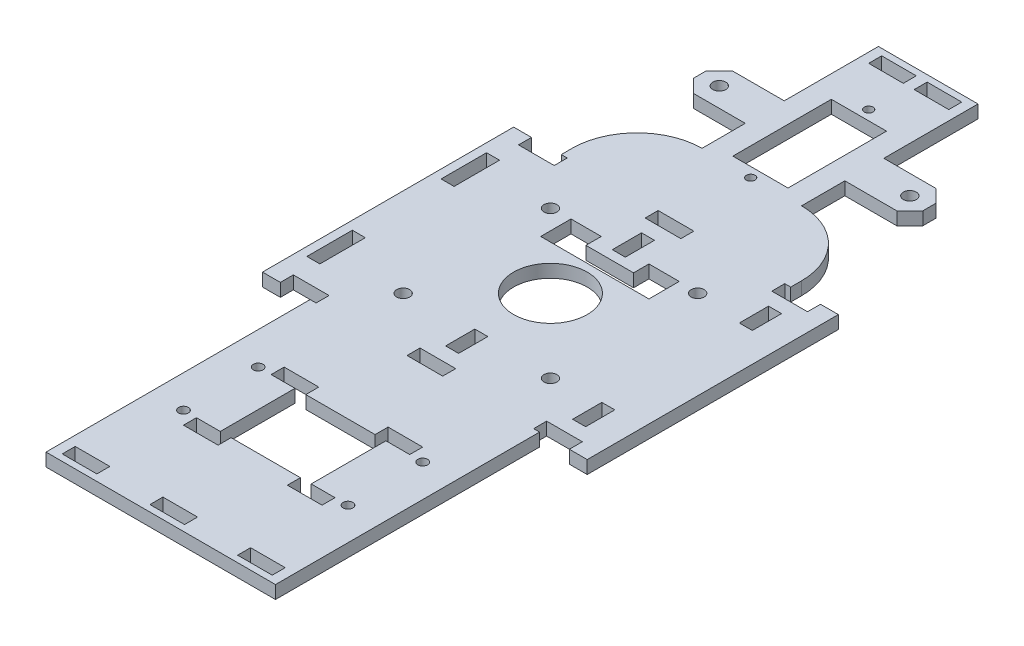
SolidWorks part; units mm, degrees
ref_plane "Front Plane" through (0, 0, 0) normal (0, 0, 1) x (1, 0, 0)
ref_plane "Top Plane" through (0, 0, 0) normal (0, 1, 0) x (1, 0, 0)
ref_plane "Right Plane" through (0, 0, 0) normal (1, 0, 0) x (0, 0, -1)
sketch "Sketch1" plane through (0, 0, 0) normal (0, 1, 0) x (1, 0, 0)
  line L1 (-12.9418, -76.5) -> (40.0582, -76.5)
  line L2 (-12.9418, -76.5) -> (-12.9418, 76.5)
  line L3 (-12.9418, 76.5) -> (40.0582, 76.5)
  line L4 (40.0582, -76.5) -> (40.0582, 76.5)
  point P0 (0, 0)
  dimension "D1" = 153
  dimension "D2" = 53
extrude "Boss-Extrude1" add sketch "Sketch1" along normal blind 3
sketch "Sketch2" plane through (0, 3, 0) normal (0, 1, 0) x (1, 0, 0)
  line L0 (-12.9418, 76.5) -> (-12.9418, -76.5) construction
  line L1 (-12.9418, -76.5) -> (40.0582, -76.5) construction
  line L2 (40.0582, -76.5) -> (40.0582, 76.5) construction
  circle A0 centre (-5.4418, -68.25) radius 1.125
  circle A1 centre (-5.4418, -51) radius 1.125
  circle A2 centre (32.5582, -68.25) radius 1.125
  circle A3 centre (32.5582, -51) radius 1.125
  dimension "D1" = 2.25
  dimension "D4" = 2.25
  dimension "D6" = 2.25
  dimension "D7" = 2.25
  dimension "D2" = 7.5
  dimension "D3" = 8.25
  dimension "D5" = 17.25
  dimension "D8" = 7.5
  dimension "D9" = 7.5
  dimension "D10" = 17.25
  dimension "D11" = 7.5
  dimension "D12" = 8.25
extrude "Cut-Extrude1" cut sketch "Sketch2" against normal blind 3
sketch "Sketch4" plane through (40.0582, 0, 0) normal (1, 0, 0) x (0, 0, -1)
  line L0 (-76.5, 3) -> (76.5, 3) construction
  line L1 (-31.5, 3) -> (26.5, 3)
  line L2 (-31.5, 3) -> (-31.5, 0)
  line L3 (-31.5, 0) -> (26.5, 0)
  line L4 (26.5, 3) -> (26.5, 0)
  line L5 (-76.5, 0) -> (76.5, 0) construction
  line L6 (76.5, 3) -> (76.5, 0) construction
  dimension "D1" = 50
  dimension "D2" = 58
extrude "Boss-Extrude3" add sketch "Sketch4" along normal blind 4.5
sketch "Sketch5" plane through (-12.9418, 0, 0) normal (-1, 0, 0) x (0, 0, 1)
  line L0 (-76.5, 0) -> (76.5, 0) construction
  line L1 (31.5, 0) -> (-26.5, 0)
  line L2 (31.5, 0) -> (31.5, 3)
  line L3 (31.5, 3) -> (-26.5, 3)
  line L4 (-26.5, 0) -> (-26.5, 3)
  line L5 (-76.5, 3) -> (76.5, 3) construction
  line L6 (-76.5, 3) -> (-76.5, 0) construction
  dimension "D1" = 50
  dimension "D2" = 58
extrude "Boss-Extrude4" add sketch "Sketch5" along normal blind 4.5
sketch "Sketch8" plane through (0, 3, 0) normal (0, 1, 0) x (1, 0, 0)
  line L1 (-12.9418, 76.5) -> (2.0582, 76.5)
  line L2 (-12.9418, 76.5) -> (-12.9418, 63)
  line L3 (-12.9418, 63) -> (2.0582, 63)
  line L4 (2.0582, 76.5) -> (2.0582, 63)
  line L5 (40.0582, 76.5) -> (25.0582, 76.5)
  line L6 (40.0582, 76.5) -> (40.0582, 63)
  line L7 (40.0582, 63) -> (25.0582, 63)
  line L8 (25.0582, 76.5) -> (25.0582, 63)
  dimension "D1" = 13.5
  dimension "D2" = 15
extrude "Cut-Extrude3" cut sketch "Sketch8" against normal blind 3
sketch "Sketch9" plane through (0, 3, 0) normal (0, 1, 0) x (1, 0, 0)
  line L1 (-12.9418, 63) -> (-6.9418, 63)
  line L2 (-12.9418, 63) -> (-12.9418, 54)
  line L3 (-12.9418, 54) -> (-6.9418, 54)
  line L4 (-6.9418, 63) -> (-6.9418, 54)
  line L5 (40.0582, 63) -> (34.0582, 63)
  line L6 (40.0582, 63) -> (40.0582, 54)
  line L7 (40.0582, 54) -> (34.0582, 54)
  line L8 (34.0582, 63) -> (34.0582, 54)
  dimension "D1" = 9
  dimension "D2" = 6
extrude "Cut-Extrude4" cut sketch "Sketch9" against normal blind 3
sketch "Sketch10" plane through (0, 3, 0) normal (0, 1, 0) x (1, 0, 0)
  line L0 (-17.4418, 26.5) -> (-12.9418, 26.5) construction
  line L1 (-12.9418, 54) -> (2.0582, 54)
  line L2 (-12.9418, 54) -> (-12.9418, 44)
  line L3 (-12.9418, 44) -> (2.0582, 44)
  line L4 (2.0582, 54) -> (2.0582, 44)
  line L5 (40.0582, 54) -> (25.0582, 54)
  line L6 (40.0582, 54) -> (40.0582, 44)
  line L7 (40.0582, 44) -> (25.0582, 44)
  line L8 (25.0582, 54) -> (25.0582, 44)
  dimension "D1" = 17.5
extrude "Cut-Extrude5" cut sketch "Sketch10" against normal blind 3
sketch "Sketch11" plane through (0, 3, 0) normal (0, 1, 0) x (1, 0, 0)
  line L0 (-17.4418, 26.5) -> (-12.9418, 26.5) construction
  line L1 (7.1832, 68.75) -> (19.9332, 68.75)
  line L2 (7.1832, 68.75) -> (7.1832, 46)
  line L3 (7.1832, 46) -> (19.9332, 46)
  line L4 (19.9332, 68.75) -> (19.9332, 46)
  line L6 (25.0582, 54) -> (25.0582, 44) construction
  dimension "D1" = 12.75
  dimension "D2" = 22.75
  dimension "D3" = 19.5
  dimension "D4" = 5.125
extrude "Cut-Extrude6" cut sketch "Sketch11" against normal blind 3
sketch "Sketch12" plane through (0, 3, 0) normal (0, 1, 0) x (1, 0, 0)
  line L0 (7.1832, 46) -> (19.9332, 46) construction
  line L1 (19.9332, 68.75) -> (7.1832, 68.75) construction
  line L2 (19.9332, 46) -> (19.9332, 68.75) construction
  circle A0 centre (13.5582, 71) radius 1
  circle A1 centre (13.5582, 43.75) radius 1
  dimension "D3" = 2
  dimension "D4" = 2
  dimension "D1" = 2.25
  dimension "D2" = 2.25
  dimension "D5" = 6.375
  dimension "D6" = 6.375
extrude "Cut-Extrude7" cut sketch "Sketch12" against normal blind 3
sketch "Sketch17" plane through (-6.9418, 0, 0) normal (-1, 0, 0) x (0, 0, 1)
  line L1 (-63, 3) -> (-54, 3)
  line L2 (-63, 3) -> (-63, 0)
  line L3 (-63, 0) -> (-54, 0)
  line L4 (-54, 3) -> (-54, 0)
extrude "Boss-Extrude6" add sketch "Sketch17" along normal blind 6
sketch "Sketch18" plane through (34.0582, 0, 0) normal (1, 0, 0) x (0, 0, -1)
  line L1 (54, 3) -> (63, 3)
  line L2 (54, 3) -> (54, 0)
  line L3 (54, 0) -> (63, 0)
  line L4 (63, 3) -> (63, 0)
extrude "Boss-Extrude8" add sketch "Sketch18" along normal blind 6
sketch "Sketch19" plane through (0, 3, 0) normal (0, 1, 0) x (1, 0, 0)
  line L0 (40.0582, 63) -> (40.0582, 54) construction
  line L1 (25.0582, 63) -> (40.0582, 63) construction
  line L2 (-12.9418, 63) -> (2.0582, 63) construction
  line L3 (-12.9418, 54) -> (-12.9418, 63) construction
  circle A0 centre (35.5582, 58.5) radius 1.5
  circle A1 centre (-8.4418, 58.5) radius 1.5
  dimension "D3" = 3
  dimension "D4" = 3
  dimension "D1" = 4.5
  dimension "D2" = 4.5
  dimension "D5" = 4.5
  dimension "D6" = 4.5
extrude "Cut-Extrude11" cut sketch "Sketch19" against normal blind 3
sketch "Sketch20" plane through (44.5582, 0, 0) normal (1, 0, 0) x (0, 0, -1)
  line L1 (-31.5, 3) -> (26.5, 3)
  line L2 (-31.5, 3) -> (-31.5, 0)
  line L3 (-31.5, 0) -> (26.5, 0)
  line L4 (26.5, 3) -> (26.5, 0)
extrude "Boss-Extrude9" add sketch "Sketch20" along normal blind 6.5
sketch "Sketch21" plane through (-17.4418, 0, 0) normal (-1, 0, 0) x (0, 0, 1)
  line L1 (-26.5, 3) -> (31.5, 3)
  line L2 (-26.5, 3) -> (-26.5, 0)
  line L3 (-26.5, 0) -> (31.5, 0)
  line L4 (31.5, 3) -> (31.5, 0)
extrude "Boss-Extrude10" add sketch "Sketch21" along normal blind 6.5
sketch "Sketch29" plane through (0, 3, 0) normal (0, 1, 0) x (1, 0, 0)
  line L1 (-2.4418, -48) -> (5.5582, -48)
  line L2 (-2.4418, -48) -> (-2.4418, -51)
  line L3 (-2.4418, -51) -> (5.5582, -51)
  line L4 (5.5582, -48) -> (5.5582, -51)
  line L5 (-2.4418, -68.25) -> (5.5582, -68.25)
  line L6 (-2.4418, -68.25) -> (-2.4418, -71.25)
  line L7 (-2.4418, -71.25) -> (5.5582, -71.25)
  line L8 (5.5582, -68.25) -> (5.5582, -71.25)
  line L9 (21.5582, -48) -> (29.5582, -48)
  line L10 (21.5582, -48) -> (21.5582, -51)
  line L11 (21.5582, -51) -> (29.5582, -51)
  line L12 (29.5582, -48) -> (29.5582, -51)
  line L13 (21.5582, -68.25) -> (29.5582, -68.25)
  line L14 (21.5582, -68.25) -> (21.5582, -71.25)
  line L15 (21.5582, -71.25) -> (29.5582, -71.25)
  line L16 (29.5582, -68.25) -> (29.5582, -71.25)
  circle A1 centre (-5.4418, -51) radius 1.125 construction
  circle A2 centre (32.5582, -51) radius 1.125 construction
  circle A3 centre (-5.4418, -68.25) radius 1.125 construction
  circle A4 centre (32.5582, -68.25) radius 1.125 construction
  dimension "D1" = 8
  dimension "D2" = 3
  dimension "D3" = 3
  dimension "D4" = 8
  dimension "D5" = 8
  dimension "D6" = 3
  dimension "D7" = 8
  dimension "D8" = 3
  dimension "D9" = 0
  dimension "D10" = 0
  dimension "D11" = 0
  dimension "D12" = 0
  dimension "D13" = 3
  dimension "D14" = 3
  dimension "D15" = 3
  dimension "D16" = 3
extrude "Cut-Extrude15" cut sketch "Sketch29" against normal blind 3
sketch "Sketch33" plane through (0, 3, 0) normal (0, 1, 0) x (1, 0, 0)
  line L0 (-2.4418, -51) -> (5.5582, -51) construction
  line L1 (3.0582, -51) -> (24.0582, -51)
  line L2 (3.0582, -51) -> (3.0582, -68.25)
  line L3 (3.0582, -68.25) -> (24.0582, -68.25)
  line L4 (24.0582, -51) -> (24.0582, -68.25)
  line L5 (29.5582, -68.25) -> (21.5582, -68.25) construction
  line L6 (-12.9418, -31.5) -> (-12.9418, -76.5) construction
  line L7 (40.0582, -76.5) -> (40.0582, -31.5) construction
  dimension "D1" = 16
  dimension "D2" = 16
extrude "Cut-Extrude20" cut sketch "Sketch33" against normal blind 3
chamfer "Chamfer1" distance 3 angle 45 1 edges at (-12.9418, 1.5, -54)
chamfer "Chamfer2" distance 3 angle 45 1 edges at (-12.9418, 1.5, -63)
chamfer "Chamfer3" distance 3 angle 45 1 edges at (40.0582, 1.5, -54)
chamfer "Chamfer4" distance 3 angle 45 1 edges at (40.0582, 1.5, -63)
sketch "Sketch34" plane through (0, 3, 0) normal (0, 1, 0) x (1, 0, 0)
  line L0 (-23.9418, 26.5) -> (-12.9418, 26.5) construction
  line L1 (-19.8168, 26.5) -> (-11.5668, 26.5)
  line L2 (-19.8168, 26.5) -> (-19.8168, 23.5)
  line L3 (-19.8168, 23.5) -> (-11.5668, 23.5)
  line L4 (-11.5668, 26.5) -> (-11.5668, 23.5)
  line L5 (51.0582, 26.5) -> (40.0582, 26.5) construction
  line L6 (46.9332, 26.5) -> (38.6832, 26.5)
  line L7 (46.9332, 26.5) -> (46.9332, 23.5)
  line L8 (46.9332, 23.5) -> (38.6832, 23.5)
  line L9 (38.6832, 26.5) -> (38.6832, 23.5)
  line L11 (-23.9418, -31.5) -> (-12.9418, -31.5) construction
  line L12 (-19.8168, -31.5) -> (-11.5668, -31.5)
  line L13 (-19.8168, -31.5) -> (-19.8168, -28.5)
  line L14 (-19.8168, -28.5) -> (-11.5668, -28.5)
  line L15 (-11.5668, -31.5) -> (-11.5668, -28.5)
  line L16 (51.0582, -31.5) -> (40.0582, -31.5) construction
  line L17 (46.9332, -31.5) -> (38.6832, -31.5)
  line L18 (46.9332, -31.5) -> (46.9332, -28.5)
  line L19 (46.9332, -28.5) -> (38.6832, -28.5)
  line L20 (38.6832, -31.5) -> (38.6832, -28.5)
  line L21 (-23.9418, -31.5) -> (-23.9418, 26.5) construction
  line L22 (9.4332, -28.5) -> (17.6832, -28.5)
  line L23 (9.4332, -28.5) -> (9.4332, -31.5)
  line L24 (9.4332, -31.5) -> (17.6832, -31.5)
  line L25 (17.6832, -28.5) -> (17.6832, -31.5)
  line L26 (9.4332, 26.5) -> (17.6832, 26.5)
  line L27 (9.4332, 26.5) -> (9.4332, 23.5)
  line L28 (9.4332, 23.5) -> (17.6832, 23.5)
  line L29 (17.6832, 26.5) -> (17.6832, 23.5)
  line L30 (51.0582, 26.5) -> (51.0582, -31.5) construction
  dimension "D1" = 4.125
  dimension "D2" = 4.125
  dimension "D3" = 8.25
  dimension "D4" = 8.25
  dimension "D5" = 8.25
  dimension "D6" = 33.375
  dimension "D7" = 8.25
  dimension "D8" = 8.25
  dimension "D9" = 8.25
  dimension "D10" = 4.125
  dimension "D11" = 4.125
  dimension "D12" = 33.375
  dimension "D13" = 3
  dimension "D14" = 3
  dimension "D15" = 3
  dimension "D16" = 3
  dimension "D17" = 3
  dimension "D18" = 3
extrude "Cut-Extrude21" cut sketch "Sketch34" against normal blind 3
sketch "Sketch35" plane through (0, 3, 0) normal (0, 1, 0) x (1, 0, 0)
  line L0 (51.0582, 26.5) -> (51.0582, -31.5) construction
  line L1 (41.3082, 20.125) -> (44.3082, 20.125)
  line L2 (41.3082, 20.125) -> (41.3082, 13.375)
  line L3 (41.3082, 13.375) -> (44.3082, 13.375)
  line L4 (44.3082, 20.125) -> (44.3082, 13.375)
  line L9 (38.6832, 23.5) -> (46.9332, 23.5) construction
  line L10 (46.9332, -28.5) -> (38.6832, -28.5) construction
  line L11 (41.3082, -18.375) -> (44.3082, -18.375)
  line L12 (41.3082, -18.375) -> (41.3082, -25.125)
  line L13 (41.3082, -25.125) -> (44.3082, -25.125)
  line L14 (44.3082, -18.375) -> (44.3082, -25.125)
  dimension "D1" = 6.75
  dimension "D2" = 6.75
  dimension "D3" = 3
  dimension "D4" = 3.375
  dimension "D5" = 3.375
  dimension "D6" = 6.75
extrude "Cut-Extrude22" cut sketch "Sketch35" against normal blind 3
sketch "Sketch36" plane through (0, 3, 0) normal (0, 1, 0) x (1, 0, 0)
  line L0 (17.6832, -28.5) -> (9.4332, -28.5) construction
  line L1 (11.9747, 20.125) -> (14.9747, 20.125)
  line L2 (11.9747, 20.125) -> (11.9747, 13.375)
  line L3 (11.9747, 13.375) -> (14.9747, 13.375)
  line L4 (14.9747, 20.125) -> (14.9747, 13.375)
  line L5 (11.9747, -18.375) -> (14.9747, -18.375)
  line L6 (11.9747, -18.375) -> (11.9747, -25.125)
  line L7 (11.9747, -25.125) -> (14.9747, -25.125)
  line L8 (14.9747, -18.375) -> (14.9747, -25.125)
  line L9 (9.4332, 23.5) -> (17.6832, 23.5) construction
  dimension "D1" = 3
  dimension "D2" = 6.75
  dimension "D3" = 3
  dimension "D4" = 6.75
  dimension "D5" = 3.375
  dimension "D6" = 3.375
extrude "Cut-Extrude23" cut sketch "Sketch36" against normal blind 3
sketch "Sketch37" plane through (0, 3, 0) normal (0, 1, 0) x (1, 0, 0)
  line L0 (-19.8168, 23.5) -> (-11.5668, 23.5) construction
  line L1 (-21.9418, 18.25) -> (-18.9418, 18.25)
  line L2 (-21.9418, 18.25) -> (-21.9418, 7.75)
  line L3 (-21.9418, 7.75) -> (-18.9418, 7.75)
  line L4 (-18.9418, 18.25) -> (-18.9418, 7.75)
  line L5 (-21.9418, -12.75) -> (-18.9418, -12.75)
  line L6 (-21.9418, -12.75) -> (-21.9418, -23.25)
  line L7 (-21.9418, -23.25) -> (-18.9418, -23.25)
  line L8 (-18.9418, -12.75) -> (-18.9418, -23.25)
  line L9 (-23.9418, -31.5) -> (-23.9418, 26.5) construction
  line L10 (-11.5668, -28.5) -> (-19.8168, -28.5) construction
  dimension "D1" = 3
  dimension "D2" = 10.5
  dimension "D3" = 5.25
  dimension "D4" = 2
  dimension "D5" = 3
  dimension "D6" = 10.5
  dimension "D7" = 5.25
  dimension "D8" = 2
extrude "Cut-Extrude24" cut sketch "Sketch37" against normal blind 3
fillet "Fillet1" radius 15 1 edges at (-12.9418, 1.5, -44)
fillet "Fillet2" radius 15 1 edges at (40.0582, 1.5, -44)
sketch "Sketch38" plane through (0, 0, -76.5) normal (0, 0, -1) x (-1, 0, 0)
  line L1 (-2.0582, 0) -> (-25.0582, 0)
  line L2 (-2.0582, 0) -> (-2.0582, 3)
  line L3 (-2.0582, 3) -> (-25.0582, 3)
  line L4 (-25.0582, 0) -> (-25.0582, 3)
extrude "Boss-Extrude12" add sketch "Sketch38" along normal blind 8.25
sketch "Sketch39" plane through (0, 0, 0) normal (0, -1, 0) x (-1, 0, 0)
  line L0 (-25.0582, 84.75) -> (-2.0582, 84.75) construction
  line L1 (-4.3082, 80.25) -> (-12.3082, 80.25)
  line L2 (-4.3082, 80.25) -> (-4.3082, 83.25)
  line L3 (-4.3082, 83.25) -> (-12.3082, 83.25)
  line L4 (-12.3082, 80.25) -> (-12.3082, 83.25)
  line L5 (-2.0582, 63) -> (-2.0582, 84.75) construction
  line L6 (-25.0582, 84.75) -> (-25.0582, 63) construction
  line L7 (-14.8082, 80.25) -> (-22.8082, 80.25)
  line L8 (-14.8082, 80.25) -> (-14.8082, 83.25)
  line L9 (-14.8082, 83.25) -> (-22.8082, 83.25)
  line L10 (-22.8082, 80.25) -> (-22.8082, 83.25)
  line L11 (-2.0582, 63) -> (-2.0582, 84.75) construction
  line L12 (-2.0582, 84.75) -> (-25.0582, 84.75) construction
  dimension "D1" = 3
  dimension "D2" = 1.5
  dimension "D3" = 8
  dimension "D4" = 2.25
  dimension "D5" = 8
  dimension "D6" = 2.25
  dimension "D7" = 3
  dimension "D8" = 1.5
extrude "Cut-Extrude25" cut sketch "Sketch39" against normal blind 3
sketch "Sketch40" plane through (0, 0, 76.5) normal (0, 0, 1) x (1, 0, 0)
  line L1 (-12.9418, 3) -> (40.0582, 3)
  line L2 (-12.9418, 3) -> (-12.9418, 0)
  line L3 (-12.9418, 0) -> (40.0582, 0)
  line L4 (40.0582, 3) -> (40.0582, 0)
extrude "Boss-Extrude13" add sketch "Sketch40" along normal blind 16
sketch "Sketch41" plane through (0, 3, 0) normal (0, 1, 0) x (1, 0, 0)
  line L0 (-12.9418, -31.5) -> (-12.9418, -92.5) construction
  line L1 (-10.6918, -88) -> (-2.6918, -88)
  line L2 (-10.6918, -88) -> (-10.6918, -91)
  line L3 (-10.6918, -91) -> (-2.6918, -91)
  line L4 (-2.6918, -88) -> (-2.6918, -91)
  line L5 (40.0582, -92.5) -> (40.0582, -31.5) construction
  line L6 (29.8082, -88) -> (37.8082, -88)
  line L7 (29.8082, -88) -> (29.8082, -91)
  line L8 (29.8082, -91) -> (37.8082, -91)
  line L9 (37.8082, -88) -> (37.8082, -91)
  line L10 (40.0582, -92.5) -> (-12.9418, -92.5) construction
  line L12 (9.5582, -88) -> (17.5582, -88)
  line L13 (9.5582, -88) -> (9.5582, -91)
  line L14 (9.5582, -91) -> (17.5582, -91)
  line L15 (17.5582, -88) -> (17.5582, -91)
  dimension "D1" = 8
  dimension "D2" = 2.25
  dimension "D3" = 8
  dimension "D4" = 2.25
  dimension "D5" = 3
  dimension "D6" = 1.5
  dimension "D7" = 1.5
  dimension "D8" = 3
  dimension "D9" = 8
  dimension "D10" = 12.25
  dimension "D11" = 3
  dimension "D12" = 1.5
extrude "Cut-Extrude26" cut sketch "Sketch41" against normal blind 3
sketch "Sketch42" plane through (0, 3, 0) normal (0, 1, 0) x (1, 0, 0)
  line L0 (8.0582, 14.75) -> (8.0582, 11.1943)
  line L1 (-6.6918, 17.75) -> (33.8082, 17.75)
  line L2 (-6.6918, 17.75) -> (-6.6918, -22.75)
  line L3 (-6.6918, -22.75) -> (33.8082, -22.75)
  line L4 (33.8082, 17.75) -> (33.8082, -22.75)
  line L5 (-23.9418, 26.5) -> (-19.8168, 26.5) construction
  line L6 (1.0582, 14.75) -> (8.0582, 14.75)
  line L7 (1.0582, 14.75) -> (1.0582, 7.75)
  line L8 (-23.9418, -31.5) -> (-23.9418, 26.5) construction
  line L9 (1.0582, 7.75) -> (26.0582, 7.75)
  line L10 (26.0582, 14.75) -> (26.0582, 7.75)
  line L11 (8.0582, 11.1943) -> (19.0582, 11.1943)
  line L12 (19.0582, 11.1943) -> (19.0582, 14.75)
  line L13 (19.0582, 14.75) -> (26.0582, 14.75)
  circle A0 centre (13.5582, -2.5) radius 8.5
  circle A1 centre (30.5582, 14.5) radius 1.5
  circle A2 centre (-3.4418, 14.5) radius 1.5
  circle A3 centre (-3.4418, -19.5) radius 1.5
  circle A4 centre (30.5582, -19.5) radius 1.5
  dimension "D9" = 3
  dimension "D12" = 3
  dimension "D13" = 3
  dimension "D16" = 3
  dimension "D25" = 17
  dimension "D1" = 40.5
  dimension "D2" = 40.5
  dimension "D3" = 8.75
  dimension "D4" = 17.25
  dimension "D5" = 20.25
  dimension "D6" = 20.25
  dimension "D7" = 3.25
  dimension "D8" = 3.25
  dimension "D10" = 3.25
  dimension "D11" = 3.25
  dimension "D14" = 3.25
  dimension "D15" = 3.25
  dimension "D17" = 3.25
  dimension "D18" = 3.25
  dimension "D19" = 7
  dimension "D20" = 10
  dimension "D21" = 25
  dimension "D22" = 7.75
  dimension "D23" = 7
  dimension "D24" = 7
extrude "Cut-Extrude30" cut sketch "Sketch42" against normal blind 3 contours A2 | L6 L0 L11 L12 L13 L10 L9 L7 | A1 | A0 | A3 | A4
